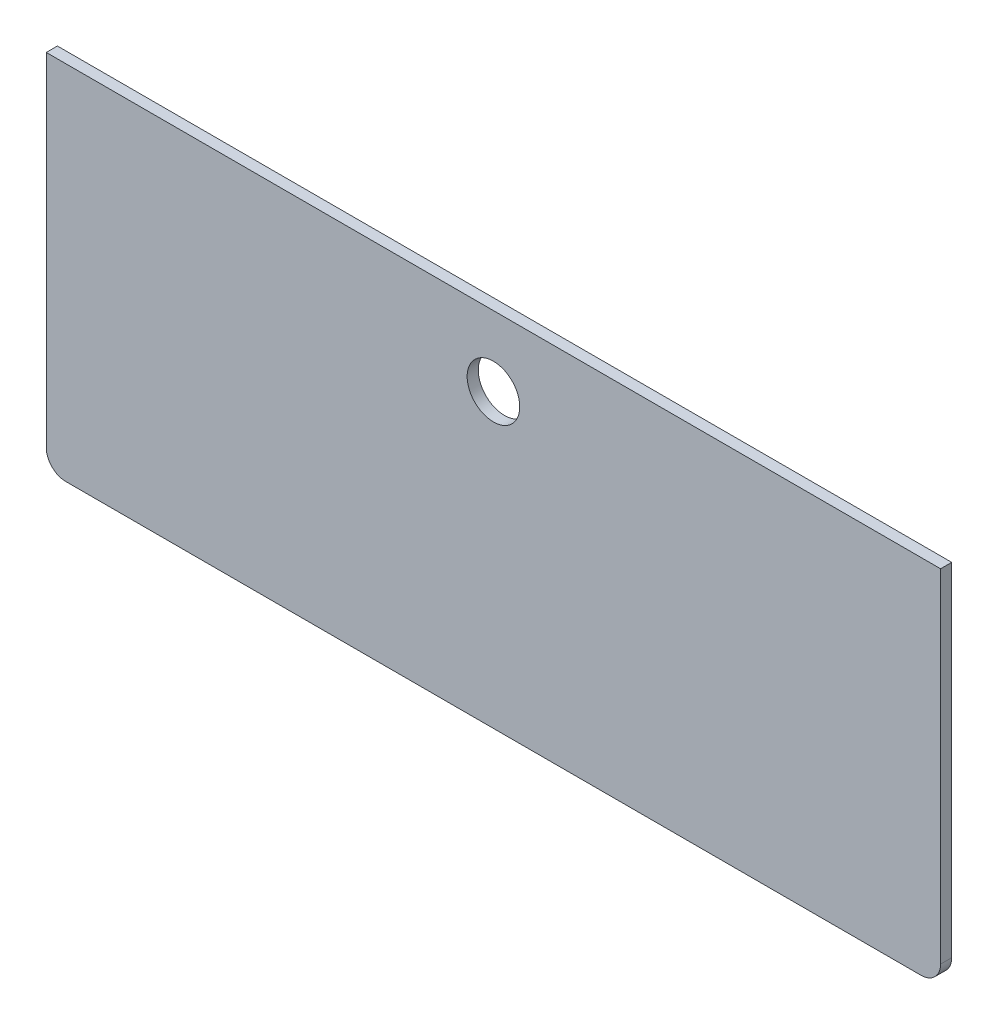
SolidWorks part; units mm, degrees
material "5052-H32"
ref_plane "Front Plane" through (0, 0, 0) normal (0, 0, 1) x (1, 0, 0)
ref_plane "Top Plane" through (0, 0, 0) normal (0, 1, 0) x (1, 0, 0)
ref_plane "Right Plane" through (0, 0, 0) normal (1, 0, 0) x (0, 0, -1)
sketch "Sketch1" plane through (0, 0, 0) normal (0, 0, 1) x (1, 0, 0)
  line L0 (-151.7654, 27.1868) -> (-151.7654, -75.9882)
  line L1 (-151.7654, -75.9882) -> (103.2346, -75.9882)
  line L2 (103.2346, -75.9882) -> (103.2346, 27.1868)
  line L3 (103.2346, 27.1868) -> (-151.7654, 27.1868)
  line L4 (-24.2654, 27.1868) -> (-24.2654, 7.1868) construction
  circle A0 centre (-24.2654, 7.1868) radius 7.5
  dimension "D4" = 15
  dimension "D1" = 103.175
  dimension "D2" = 255
  dimension "D3" = 20
extrude "Boss-Extrude1" add sketch "Sketch1" along normal blind 3.175
fillet "Fillet1" radius 5.5562 2 edges at (-151.7654, -75.9882, 1.5875) (103.2346, -75.9882, 1.5875)
equation "\"L\"= 400"
equation "\"W\"= 255"
equation "\"H\"= 110"
equation "\"Compartment Width\"= 80"
equation "\"T\"= 4.7625 * 2 / 3"
equation "\"Inside Fillet Radius\"= 5.55625"
equation "\"D1@Boss-Extrude1\"=\"T\""
equation "\"D1@Fillet1\"=\"Inside Fillet Radius\""
equation "\"Hole\"=15"
equation "\"D4@Sketch1\"=\"Hole\""
equation "\"D2@Sketch1\"=\"W\""
equation "\"D1@Sketch1\"=\"H\"+\"T\"-10"
equation "\"Offset\"= 30"
equation "\"Wheel to Wall\"= 50"
